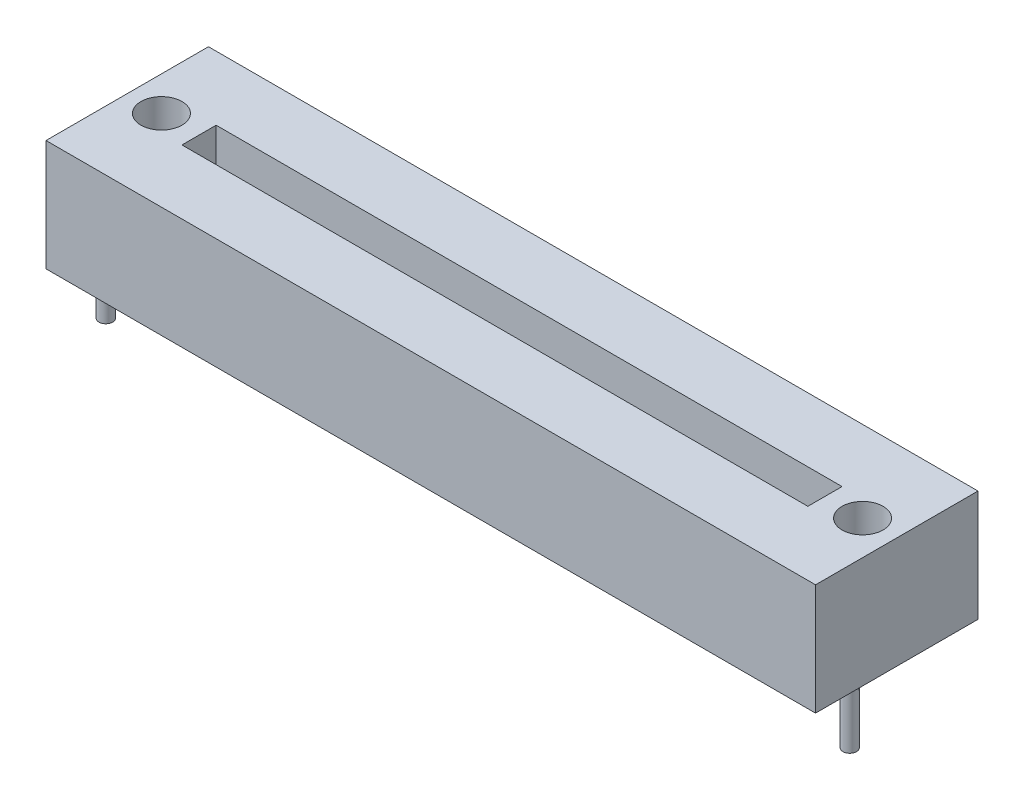
SolidWorks part; units mm, degrees
ref_plane "Front Plane" through (0, 0, 0) normal (0, 0, 1) x (1, 0, 0)
ref_plane "Top Plane" through (0, 0, 0) normal (0, 1, 0) x (1, 0, 0)
ref_plane "Right Plane" through (0, 0, 0) normal (1, 0, 0) x (0, 0, -1)
sketch "Sketch1" plane through (0, 0, 0) normal (0, 1, 0) x (1, 0, 0)
  line L1 (-22.5, -4.75) -> (22.5, -4.75)
  line L2 (-22.5, -4.75) -> (-22.5, 4.75)
  line L3 (-22.5, 4.75) -> (22.5, 4.75)
  line L4 (22.5, -4.75) -> (22.5, 4.75)
  line L5 (-22.5, -4.75) -> (22.5, 4.75) construction
  line L6 (-22.5, 4.75) -> (22.5, -4.75) construction
  line L7 (-18.3, -1) -> (18.3, -1)
  line L8 (-18.3, -1) -> (-18.3, 1)
  line L9 (-18.3, 1) -> (18.3, 1)
  line L10 (18.3, -1) -> (18.3, 1)
  line L11 (-18.3, -1) -> (18.3, 1) construction
  line L12 (-18.3, 1) -> (18.3, -1) construction
  point P0 (0, 0)
  point P6 (0, 0)
  dimension "D1" = 45
  dimension "D2" = 9.5
  dimension "D3" = 2
  dimension "D4" = 36.6
extrude "Boss-Extrude1" add sketch "Sketch1" along normal blind 6.5
sketch "Sketch2" plane through (0, 0, 0) normal (0, -1, 0) x (1, 0, 0)
  line L0 (22.5, 4.75) -> (22.5, -4.75) construction
  line L1 (22.5, -4.75) -> (-22.5, -4.75) construction
  line L2 (-22.5, -4.75) -> (-22.5, 4.75) construction
  line L3 (-22.5, 4.75) -> (22.5, 4.75) construction
  line L4 (22.5, 4.75) -> (22.5, -4.75)
  line L5 (22.5, -4.75) -> (-22.5, -4.75)
  line L6 (-22.5, -4.75) -> (-22.5, 4.75)
  line L7 (-22.5, 4.75) -> (22.5, 4.75)
extrude "Boss-Extrude2" add sketch "Sketch2" against normal blind 2
sketch "Sketch3" plane through (0, 6.5, 0) normal (0, 1, 0) x (1, 0, 0)
  line L0 (-20.5, 0) -> (20.5, 0) construction
  circle A0 centre (-20.5, 0) radius 1
  circle A1 centre (20.5, 0) radius 1
  point P0 (-20.5, 0)
  point P1 (20.5, 0)
  point P2 (0, 0)
  point P9 (-20.5, 0)
  point P13 (20.5, 0)
  dimension "D2" = 2
  dimension "D1" = 41
hole_wizard "M2 Clearance Hole1" positions "Sketch3" profile "Sketch4" hole size "M2" standard "ANSI Metric" end condition through all
sketch "Sketch4" plane through (20.5, 6.5, 0) normal (1, 0, 0) x (0, 0, 1)
  line L0 (0, 0) -> (0, 6.5)
  line L1 (0, 6.5) -> (1.2, 6.5)
  line L2 (1.2, 6.5) -> (1.2, 0)
  line L5 (1.2, 0) -> (0, 0)
  line L11 (0, -6.35) -> (0, 107.95) construction
  dimension "Thru Hole Dia." = 2.4
  dimension "Thru Hole Depth" = 6.5
sketch "Sketch5" plane through (0, 0, 0) normal (0, -1, 0) x (1, 0, 0)
  line L1 (-21.75, -2) -> (21.75, -2) construction
  line L2 (-21.75, -2) -> (-21.75, 2) construction
  line L3 (-21.75, 2) -> (21.75, 2) construction
  line L4 (21.75, -2) -> (21.75, 2) construction
  line L5 (-21.75, -2) -> (21.75, 2) construction
  line L6 (-21.75, 2) -> (21.75, -2) construction
  circle A0 centre (-21.75, 2) radius 0.4
  circle A1 centre (-21.75, -2) radius 0.4
  circle A3 centre (21.75, 2) radius 0.4
  point P0 (0, 0)
  dimension "D3" = 0.8
  dimension "D1" = 43.5
  dimension "D2" = 4
extrude "Boss-Extrude3" add sketch "Sketch5" along normal blind 3.5
